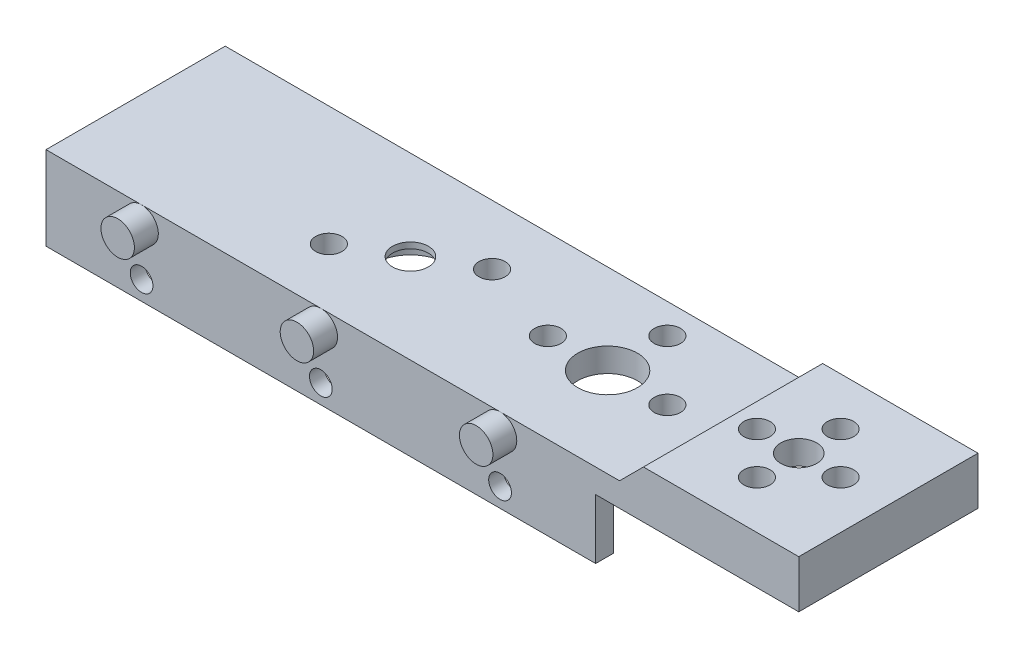
SolidWorks part; units mm, degrees
note: The reader was unsure of these and kept them because the rebuilt part matched: shared geometry of "草图2<3>", "草图1<7>", "草图1<8>".
ref_plane "前视基准面" through (0, 0, 0) normal (0, 0, 1) x (1, 0, 0)
ref_plane "上视基准面" through (0, 0, 0) normal (0, 1, 0) x (1, 0, 0)
ref_plane "右视基准面" through (0, 0, 0) normal (1, 0, 0) x (0, 0, -1)
other "Configuration Table"
sketch "草图1" plane through (0, 0, 0) normal (0, 1, 0) x (1, 0, 0)
  line L0 (-31.5, 7.5) -> (31.5, 7.5)
  line L1 (31.5, 7.5) -> (31.5, -7.5)
  line L2 (31.5, -7.5) -> (-31.5, -7.5)
  line L3 (-31.5, -7.5) -> (-31.5, 7.5)
  line L4 (-31.5, 0) -> (31.5, 0) construction
  line L5 (-12.8301, -2.5) -> (-4.1699, 2.5) construction
  line L6 (-13.3083, -5.95) -> (-3.6917, -5.95) construction
  line L7 (-13.3083, 5.95) -> (-3.6917, 5.95) construction
  line L8 (-8.5, 0) -> (-8.5, 4.4384) construction
  line L10 (31.5, 7.5) -> (16.5, 7.5)
  line L11 (31.5, 7.5) -> (31.5, -7.5)
  line L12 (31.5, -7.5) -> (16.5, -7.5)
  line L13 (16.5, 7.5) -> (16.5, -7.5)
  circle A0 centre (-8.5, 0) radius 1.5
  circle A1 centre (-4.1699, 2.5) radius 1.1
  circle A3 centre (-12.8301, -2.5) radius 1.1
  arc A4 (-13.3083, 5.95) -> (-13.3083, -5.95) centre (-8.5, 0) ccw construction
  circle A5 centre (8, 0) radius 2.5
  arc A6 (-3.6917, -5.95) -> (-3.6917, 5.95) centre (-8.5, 0) ccw construction
  circle A7 centre (24, 0) radius 1.5
  circle A8 centre (24, 0) radius 3.5 construction
  circle A9 centre (27.5, 0) radius 1.1
  circle A10 centre (24, -3.5) radius 1.1
  circle A11 centre (20.5, 0) radius 1.1
  circle A12 centre (24, 3.5) radius 1.1
  circle A13 centre (-4.1699, -2.5) radius 1.1
  circle A14 centre (-12.8301, 2.5) radius 1.1
  circle A15 centre (13, 0) radius 1.1
  circle A17 centre (3, 0) radius 1.1
  circle A18 centre (8, 5) radius 1.1
  circle A19 centre (8, -5) radius 1.1 [skipped]
  circle A20 centre (24, 0) radius 6
  point P5 (0, 7.5)
  point P7 (-31.5, 0)
  dimension "D3" = 3
  dimension "D6" = 2.2
  dimension "D9" = 15.3
  dimension "D12" = 5
  dimension "D14" = 3
  dimension "D15" = 7
  dimension "D16" = 2.2
  dimension "D18" = 2.2
  dimension "D22" = 12
  dimension "D1" = 63
  dimension "D2" = 15
  dimension "D4" = 23
  dimension "D7" = 30
  dimension "D8" = 10
  dimension "D10" = 11.9
  dimension "D11" = 16.5
  dimension "D13" = 16
  dimension "D19" = 5
  dimension "D21" = 15
  dimension "D5" = 2
  dimension "D17" = 4
  dimension "D20" = 4
extrude "凸台-拉伸1" add sketch "草图1" along normal blind 2 contours A3 | L3 L2 L1 L0 A13 A12 A11 A10 A9 A7 A5 A3 A1 A0 A14 | A1 | L11 L10 L13 L12
sketch "草图2" plane through (0, 0, 7.5) normal (0, 0, 1) x (1, 0, 0)
  line L0 (-31, 0.6) -> (31, 0.6) construction
  line L1 (-31.5, 2) -> (-31.5, 0) construction
  line L3 (31.5, 2) -> (-31.5, 2) construction
  circle A0 centre (-23.5, 0.6) radius 1.4
  circle A1 centre (-8.5, 0.6) radius 1.4
  circle A2 centre (6.5, 0.6) radius 1.4
  circle A3 centre (-23.5, -3.4) radius 0.95
  circle A4 centre (-8.5, -3.4) radius 0.95
  circle A5 centre (6.5, -3.4) radius 0.95
  line M13 (-31.5, 0) -> (31.5, 0)
  dimension "D1" = 2.8
  dimension "D2" = 2.8
  dimension "D3" = 2.8
  dimension "D8" = 1.9
  dimension "D4" = 15
  dimension "D5" = 15
  dimension "D6" = 8
  dimension "D7" = 1.4
  dimension "D9" = 4
  dimension "D10" = 3
extrude "凸台-拉伸2" add sketch "草图2" along normal blind 2 contours A0 L0 | L0 A0 M13 | A0 M13 | A1 L0 | L0 A1 M13 | A2 L0 | L0 A2 M13 | A2 M13
sketch "草图3" plane through (0, 0, 0) normal (0, -1, 0) x (1, 0, 0)
  circle A0 centre (-8.5, 0) radius 3
  dimension "D1" = 6
extrude "切除-拉伸1" cut sketch "草图3" against normal blind 1.5
sketch "草图4" plane through (0, 0, 0) normal (0, -1, 0) x (1, 0, 0)
  line L1 (-31.5, 7.5) -> (14.5, 7.5)
  line L2 (-31.5, 7.5) -> (-31.5, 6)
  line L3 (-31.5, 6) -> (14.5, 6)
  line L4 (14.5, 7.5) -> (14.5, 6)
  dimension "D1" = 46
  dimension "D2" = 1.5
extrude "凸台-拉伸3" add sketch "草图4" along normal blind 5
extrude "切除-拉伸2" cut sketch "草图2<3>" against normal up to surface (1.5 mm away) contours A3 | A4 | A5 up to face at (-8.5, -2.5, 6)
sketch "草图2<3>" plane through (0, 0, 7.5) normal (0, 0, 1) x (1, 0, 0) same geometry as "草图2"
sketch "草图5" plane through (0, 0, 6) normal (0, 0, -1) x (-1, 0, 0)
  line L0 (22.403, -1.5) -> (24.597, -1.5)
  line L1 (24.597, -1.5) -> (25.6939, -3.4)
  line L2 (25.6939, -3.4) -> (24.597, -5.3)
  line L3 (24.597, -5.3) -> (22.403, -5.3)
  line L4 (22.403, -5.3) -> (21.3061, -3.4)
  line L5 (21.3061, -3.4) -> (22.403, -1.5)
  line L6 (21.3061, -3.4) -> (25.6939, -3.4) construction
  line L7 (24.597, -1.5) -> (22.403, -5.3) construction
  line L8 (6.3061, -3.4) -> (7.403, -1.5)
  line L9 (7.403, -1.5) -> (9.597, -1.5)
  line L10 (9.597, -1.5) -> (10.6939, -3.4)
  line L11 (10.6939, -3.4) -> (9.597, -5.3)
  line L12 (9.597, -5.3) -> (7.403, -5.3)
  line L13 (7.403, -5.3) -> (6.3061, -3.4)
  line L14 (-8.6939, -3.4) -> (-7.597, -1.5)
  line L15 (-7.597, -1.5) -> (-5.403, -1.5)
  line L16 (-5.403, -1.5) -> (-4.3061, -3.4)
  line L17 (-4.3061, -3.4) -> (-5.403, -5.3)
  line L18 (-5.403, -5.3) -> (-7.597, -5.3)
  line L19 (-7.597, -5.3) -> (-8.6939, -3.4)
  line L20 (7.403, -1.5) -> (9.597, -5.3) construction
  line L21 (7.403, -5.3) -> (9.597, -1.5) construction
  circle A0 centre (23.5, -3.4) radius 0.95
  circle A1 centre (8.5, -3.4) radius 0.95
  circle A2 centre (8.5, -3.4) radius 0.95 construction
  circle A3 centre (23.5, -3.4) radius 0.95 construction
  point P17 (23.5, -3.4)
  dimension "D1" = 120
  dimension "D2" = 120
  dimension "D3" = 120
  dimension "D4" = 3.8
  dimension "D5" = 3.8
  dimension "D6" = 3.8
  dimension "D7" = 3
extrude "切除-拉伸3" cut sketch "草图5" against normal blind 0.25 contours L14 L15 L16 L17 L18 L19 | L8 L9 L10 L11 L12 L13 | L5 L0 L1 L2 L3 L4
extrude "凸台-拉伸4" add sketch "草图1<7>" along normal blind 4 contours L11 L10 L13 L12 | A12 | A9 | A10 | A7 | A11
sketch "草图1<7>" plane through (0, 0, 0) normal (0, 1, 0) x (1, 0, 0) same geometry as "草图1"
extrude "切除-拉伸4" cut sketch "草图1<8>" along normal blind 2 contours A20 A7 A9 A10 A11 A12
sketch "草图1<8>" plane through (0, 0, 0) normal (0, 1, 0) x (1, 0, 0) same geometry as "草图1"
sketch "草图6" plane through (0, 0, -7.5) normal (0, 0, -1) x (-1, 0, 0)
  line L0 (-16.5, 2) -> (-18.5, 4)
  line L1 (-31.5, 4) -> (-16.5, 4) construction
  line L2 (-18.5, 4) -> (-16.5, 4)
  line L3 (-16.5, 4) -> (-16.5, 2) construction
  line L4 (-16.5, 4) -> (-16.5, 2)
  dimension "D1" = 45
extrude "切除-拉伸5" cut sketch "草图6" against normal up to surface (15 mm away) up to face at (1.0857, 0.7, 7.5)
